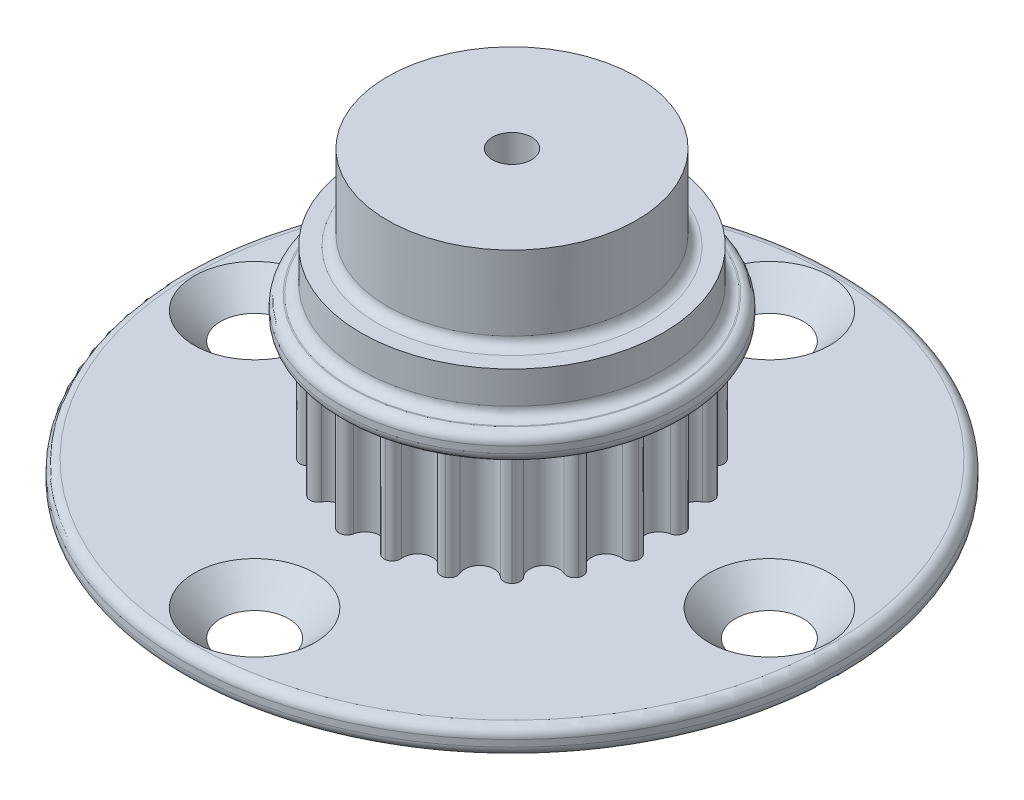
SolidWorks part; units mm, degrees
ref_plane "Front Plane" through (0, 0, 0) normal (0, 0, 1) x (1, 0, 0)
ref_plane "Top Plane" through (0, 0, 0) normal (0, 1, 0) x (1, 0, 0)
ref_plane "Right Plane" through (0, 0, 0) normal (1, 0, 0) x (0, 0, -1)
sketch "Sketch1" plane through (0, 0, 0) normal (0, 1, 0) x (1, 0, 0)
  line L0 (0, 0) -> (0, 9.1676) construction
  line L1 (0, 0) -> (2.731, 8.405) construction
  circle A0 centre (0, 0) radius 9.1676 construction
  circle A1 centre (0, 0) radius 7.9476 construction
  circle A2 centre (0, 8.8376) radius 0.89 construction
  circle A5 centre (2.731, 8.405) radius 0.89 construction
  arc A6 (0, 7.9476) -> (0.8721, 8.6598) centre (0, 8.8376) ccw
  arc A7 (0.8721, 8.6598) -> (1.4405, 9.0537) centre (1.362, 8.5599) cw
  arc A8 (1.4277, 9.0557) -> (1.8466, 8.5054) centre (1.3498, 8.5618) cw
  arc A9 (2.4559, 7.5586) -> (1.8466, 8.5054) centre (2.731, 8.405) cw
  arc A10 (1.4405, 9.0537) -> (1.4277, 9.0557) centre (0, 0) cw
  arc A11 (0, 7.9476) -> (2.4559, 7.5586) centre (0, 0) ccw
  dimension "D1" = 18.3352
  dimension "D3" = 1.78
  dimension "D4" = 0.5
  dimension "D2" = 1.22
  dimension "D5" = 18
extrude "Boss-Extrude1" add sketch "Sketch1" along normal mid plane 7.112 contours A6 A11 A9 A8 A7 region at (0.0089, 0, -0.0564)
ref_axis "Axis1" through (0, 3.3, 0) along (0, -1, 0)
pattern_circular "CirPattern1" count 20 over 360 about axis through (0, 3.3, 0) along (0, -1, 0) of "Boss-Extrude1"
sketch "Sketch2" plane through (0, 0, 0) normal (1, 0, 0) x (0, 0, -1)
  line L10 (0, 3.5) -> (10.3423, 3.5) construction
  line L11 (0, 3.5) -> (0, 5.0875) construction
  line L12 (0, 5.0875) -> (10.3423, 5.0875)
  line L15 (10.3423, 3.5) -> (10.3423, 5.0875) construction
  line L20 (0, 3.3) -> (0, -3.3) construction
  line L22 (10.3423, 5.0875) -> (0, 5.0875) construction
  line L23 (10.3423, 5.0875) -> (10.3423, 3.5)
  line L24 (10.3423, 3.5) -> (0, 3.5)
  line L25 (0, 5.0875) -> (0, 3.5)
  dimension "D1" = 1.5875
  dimension "D2" = 10.3423
  dimension "D3" = 3.5
revolve "Revolve3" add sketch "Sketch2" angle 360 about axis through (0, 3.3, 0) along (0, -1, 0) region at (0, 4.2937, -5.1712)
mirror "Mirror1" about plane through (0, 0, 0) normal (0, 1, 0) of "Revolve3"
sketch "Sketch9" plane through (0, -5.0875, 0) normal (0, -1, 0) x (1, 0, 0)
  circle A0 centre (0, 0) radius 19.8438
  circle A1 centre (0, 0) radius 1.5
  dimension "D1" = 3
  dimension "D2" = 39.6875
extrude "Boss-Extrude2" add sketch "Sketch9" against normal up to surface (1.5875 mm away) up to face at (0, -3.5, 0)
sketch "Sketch3" plane through (0, 0, 0) normal (0, 1, 0) x (1, 0, 0)
  circle A0 centre (-15.5, 0) radius 1.7462
  circle A3 centre (0, 15.5) radius 1.7462
  circle A4 centre (15.5, 0) radius 1.7463
  circle A5 centre (0, -15.5) radius 1.7462
  dimension "D3" = 3.4925
  dimension "D1" = 15.5
  dimension "D4" = 4
extrude "Cut-Extrude1" cut sketch "Sketch3" against normal through all both and the other way through all
ref_axis "Axis2" through (-15.5, -5.0875, 0) along (0, 1, 0)
sketch "Sketch6" plane through (0, 0, 0) normal (0, 0, 1) x (1, 0, 0)
  line L0 (-19.1322, -3.5) -> (-11.8678, -3.5) construction
  line L1 (-13.7538, -3.5) -> (-17.2462, -3.5) construction
  line L2 (-11.8678, -3.5) -> (-15.5, -7.1322)
  line L3 (-15.5, -7.1322) -> (-19.1322, -3.5) construction
  line L4 (-18.548, -4.0842) -> (-12.452, -4.0842) construction
  line L5 (-17.2462, -3.998) -> (-13.7538, -3.998) construction
  line L8 (-15.5, -7.1322) -> (-15.5, -3.5)
  line L9 (-15.5, -3.5) -> (-11.8678, -3.5)
  line L10 (-15.5, -5.0875) -> (-15.5, -3.5) construction
  line L12 (-17.2462, -3.5) -> (-17.2462, -5.0875) construction
  line L13 (-13.7538, -5.0875) -> (-13.7538, -3.5) construction
  point P2 (-15.5, -3.998)
  dimension "D1" = 6.096
  dimension "D2" = 0.5842
revolve "Cut-Revolve2" cut sketch "Sketch6" angle 360 about axis through (-15.5, -5.0875, 0) along (0, 1, 0)
pattern_circular "CirPattern2" count 4 over 360 about axis through (0, 3.3, 0) along (0, -1, 0) of "Cut-Revolve2"
sketch "Sketch10" plane through (0, 0, 0) normal (1, 0, 0) x (0, 0, -1)
  line L1 (1.1822, 7.6275) -> (7.5, 7.6275) construction
  line L2 (1.1822, 7.6275) -> (1.1822, 12.7075)
  line L3 (1.1822, 12.7075) -> (7.5, 12.7075)
  line L4 (7.5, 7.6275) -> (7.5, 12.7075)
  line L5 (0, 0) -> (0, 12.7075) construction
  line L6 (10.3423, 5.0875) -> (-10.3423, 5.0875) construction
  line L7 (1.1822, 7.6275) -> (9.0875, 7.6275) construction
  line L8 (1.1822, 7.6275) -> (1.1822, 5.0875)
  line L9 (1.1822, 5.0875) -> (9.0875, 5.0875)
  line L10 (9.0875, 7.6275) -> (9.0875, 5.0875)
  line L11 (7.5, 7.6275) -> (9.0875, 7.6275)
  line L12 (0, 12.7075) -> (1.1822, 12.7075) construction
  dimension "D1" = 2.3644
  dimension "D2" = 5.08
  dimension "D3" = 1.5875
  dimension "D4" = 2.54
  dimension "D5" = 15
revolve "Revolve4" add sketch "Sketch10" angle 360 about L5
fillet "Fillet1" radius 0.5953 6 edges at (0, 5.0875, 10.3423) (0, 3.5, 10.3423) (0, -3.5, 19.8438) (0, -5.0875, -19.8438) (0, 7.6275, -7.5) (0, 5.0875, -9.0875)
sketch "Sketch11" plane through (0, -5.0875, 0) normal (0, -1, 0) x (1, 0, 0)
  circle A0 centre (0, 0) radius 1.5
  dimension "D1" = 3
extrude "Cut-Extrude2" cut sketch "Sketch11" against normal blind 6
equation "\"TEETH_NUM\"= 20"
equation "\"TOOTH_PITCH\"= 3mm"
equation "\"PITCH_LINE_OFFSET\"= .015in"
equation "\"DIAMETER_PER_GROOVE\"= \"OUTSIDE_DIAMETER\" / \"TEETH_NUM\" * 1in"
equation "\"PITCH_DIAMETER\"= ( ( \"TEETH_NUM\" * 3 - 1.31 ) / 3.1415 + .415 ) * 1mm"
equation "\"OUTSIDE_DIAMETER\"= \"PITCH_DIAMETER\" - \"PITCH_LINE_OFFSET\" * 2"
equation "\"D1@Sketch1\"=\"OUTSIDE_DIAMETER\""
equation "\"TOOTH_HEIGHT\"= 1.22mm"
equation "\"D2@Sketch1\"=\"TOOTH_HEIGHT\""
equation "\"TOOTH_DIAMETER\"= 1.78mm"
equation "\"INTERNAL_RADIUS\"= .5mm"
equation "\"D3@Sketch1\"=\"TOOTH_DIAMETER\""
equation "\"D5@Sketch1\"=360 / \"TEETH_NUM\""
equation "\"D4@Sketch1\"=\"INTERNAL_RADIUS\""
equation "\"D1@CirPattern1\"=\"TEETH_NUM\""
equation "\"BELT_GAP\"= 7mm"
equation "\"D2@Sketch2\"=\"PITCH_DIAMETER\"/2+1/32"
equation "\"D3@Sketch2\"=\"BELT_GAP\"/2"
